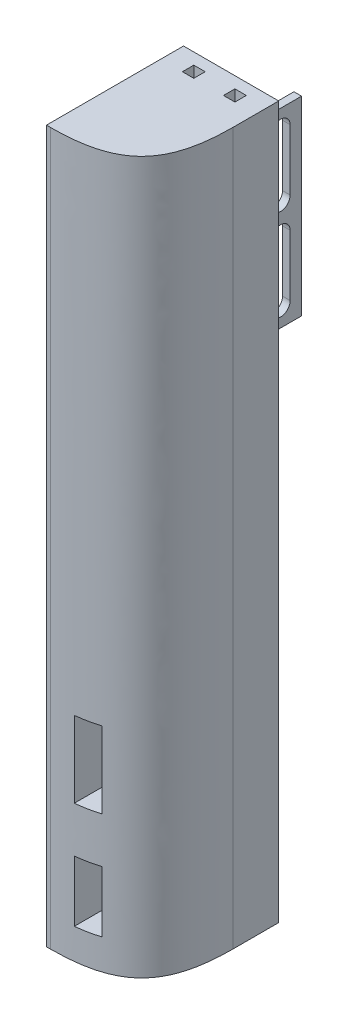
SolidWorks part; units mm, degrees
ref_plane "Front Plane" through (0, 0, 0) normal (0, 0, 1) x (1, 0, 0)
ref_plane "Top Plane" through (0, 0, 0) normal (0, 1, 0) x (1, 0, 0)
ref_plane "Right Plane" through (0, 0, 0) normal (1, 0, 0) x (0, 0, -1)
sketch "Sketch1" plane through (0, 0, 0) normal (0, 1, 0) x (1, 0, 0)
  line L1 (0, 0) -> (25, 0)
  line L2 (0, 0) -> (0, 36)
  line L3 (0, 36) -> (25, 36)
  line L4 (25, 0) -> (25, 36)
  dimension "D1" = 36
  dimension "D2" = 25
extrude "Boss-Extrude1" add sketch "Sketch1" along normal blind 186.9
fillet "Fillet1" radius 24 1 edges at (25, 93.45, 0) conic rho 0.55
sketch "Sketch2" plane through (0, 0, 0) normal (-1, 0, 0) x (0, 0, 1)
  line L0 (-24, 0) -> (0, 0) construction
  line L1 (-6.2, 83.2) -> (-1.2, 83.2)
  line L2 (-6.2, 83.2) -> (-6.2, 73.2)
  line L3 (-6.2, 73.2) -> (-1.2, 73.2)
  line L4 (-1.2, 83.2) -> (-1.2, 73.2)
  line L5 (0, 186.9) -> (0, 0) construction
  dimension "D1" = 73.2
  dimension "D2" = 1.2
  dimension "D3" = 5
  dimension "D4" = 10
extrude "Cut-Extrude1" cut sketch "Sketch2" against normal blind 4
sketch "Sketch3" plane through (0, 0, 0) normal (-1, 0, 0) x (0, 0, 1)
  line L1 (-14, 33.2) -> (-6, 33.2)
  line L2 (-14, 33.2) -> (-14, 28)
  line L3 (-14, 28) -> (-6, 28)
  line L4 (-6, 33.2) -> (-6, 28)
  line L5 (-36, 0) -> (0, 0) construction
  line L6 (0, 186.9) -> (0, 0) construction
  line L8 (-22, 33.2) -> (-30, 33.2)
  line L9 (-22, 33.2) -> (-22, 28)
  line L10 (-22, 28) -> (-30, 28)
  line L11 (-30, 33.2) -> (-30, 28)
  line L12 (-6, 61.2) -> (-14, 61.2)
  line L13 (-6, 61.2) -> (-6, 66.8)
  line L14 (-6, 66.8) -> (-14, 66.8)
  line L15 (-14, 61.2) -> (-14, 66.8)
  line L16 (-22, 66.8) -> (-30, 66.8)
  line L17 (-22, 66.8) -> (-22, 61.2)
  line L18 (-22, 61.2) -> (-30, 61.2)
  line L19 (-30, 66.8) -> (-30, 61.2)
  dimension "D1" = 28
  dimension "D2" = 6
  dimension "D3" = 8
  dimension "D4" = 5.2
  dimension "D5" = 8
  dimension "D6" = 8
  dimension "D7" = 28
  dimension "D8" = 5.6
  dimension "D9" = 8
  dimension "D10" = 6
  dimension "D11" = 8
  dimension "D12" = 5.6
  dimension "D13" = 8
extrude "Cut-Extrude2" cut sketch "Sketch3" against normal blind 10
sketch "Sketch4" plane through (0, 0, 0) normal (-1, 0, 0) x (0, 0, 1)
  line L0 (-36, 0) -> (0, 0) construction
  line L1 (-26, 160) -> (-67, 160)
  line L2 (-26, 160) -> (-26, 110)
  line L3 (-26, 110) -> (-67, 110)
  line L4 (-67, 160) -> (-67, 110)
  line L5 (-36, 186.9) -> (-36, 0) construction
  dimension "D1" = 160
  dimension "D2" = 10
  dimension "D3" = 31
  dimension "D4" = 110
extrude "Boss-Extrude2" add sketch "Sketch4" along normal blind 2
sketch "Sketch5" plane through (-2, 0, 0) normal (-1, 0, 0) x (0, 0, 1)
  line L0 (-67, 110) -> (-26, 110) construction
  line L1 (-67, 160) -> (-67, 110) construction
  line L4 (-59, 131) -> (-59, 115)
  line L6 (-64, 131) -> (-64, 115)
  line L7 (-26, 160) -> (-67, 160) construction
  line L9 (-64, 139) -> (-64, 155)
  line L11 (-59, 139) -> (-59, 155)
  arc A0 (-64, 115) -> (-59, 115) centre (-61.5, 115) ccw
  arc A2 (-59, 131) -> (-64, 131) centre (-61.5, 131) ccw
  arc A3 (-59, 155) -> (-64, 155) centre (-61.5, 155) ccw
  arc A4 (-64, 139) -> (-59, 139) centre (-61.5, 139) ccw
  dimension "D1" = 5
  dimension "D4" = 16
  dimension "D5" = 16
  dimension "D2" = 5
  dimension "D3" = 5.5
  dimension "D6" = 5
extrude "Cut-Extrude3" cut sketch "Sketch5" against normal up to next
chamfer "Chamfer1" distance 16 angle 45 1 edges at (0, 135, -36)
sketch "Sketch6" plane through (0, 0, -36) normal (0, 0, -1) x (-1, 0, 0)
  line L0 (-25, 186.9) -> (-25, 0) construction
  line L1 (-21, 182.9) -> (-15, 182.9)
  line L2 (-21, 182.9) -> (-21, 178.9)
  line L3 (-21, 178.9) -> (-15, 178.9)
  line L4 (-15, 182.9) -> (-15, 178.9)
  line L5 (-25, 186.9) -> (0, 186.9) construction
  line L6 (-1, 186.9) -> (-25, 186.9) construction
  line L7 (-10.2, 182.9) -> (-4.2, 182.9)
  line L8 (-10.2, 182.9) -> (-10.2, 178.9)
  line L9 (-10.2, 178.9) -> (-4.2, 178.9)
  line L10 (-4.2, 182.9) -> (-4.2, 178.9)
  dimension "D1" = 4
  dimension "D2" = 4
  dimension "D3" = 4
  dimension "D4" = 6
  dimension "D5" = 6
  dimension "D6" = 4.8
  dimension "D7" = 4
extrude "Cut-Extrude4" cut sketch "Sketch6" against normal blind 9
sketch "Sketch7" plane through (0, 186.9, 0) normal (0, 1, 0) x (1, 0, 0)
  line L0 (25, 24) -> (25, 36) construction
  line L1 (19.5, 33) -> (16.5, 33)
  line L2 (19.5, 33) -> (19.5, 30)
  line L3 (19.5, 30) -> (16.5, 30)
  line L4 (16.5, 33) -> (16.5, 30)
  line L5 (25, 36) -> (0, 36) construction
  line L7 (8.7, 33) -> (5.7, 33)
  line L8 (8.7, 33) -> (8.7, 30)
  line L9 (8.7, 30) -> (5.7, 30)
  line L10 (5.7, 33) -> (5.7, 30)
  dimension "D1" = 5.5
  dimension "D2" = 3
  dimension "D3" = 3
  dimension "D4" = 3
  dimension "D5" = 3
  dimension "D6" = 3
  dimension "D7" = 3
  dimension "D8" = 7.8
extrude "Cut-Extrude5" cut sketch "Sketch7" against normal blind 10
sketch "Sketch8" plane through (0, 0, 0) normal (0, -1, 0) x (1, 0, 0)
  line L0 (25, -36) -> (0, -36) construction
  line L1 (3, -5) -> (7, -5)
  line L2 (3, -5) -> (3, -33)
  line L3 (3, -33) -> (7, -33)
  line L4 (7, -5) -> (7, -29)
  line L5 (0, -36) -> (0, 0) construction
  line L6 (25, -24) -> (25, -36) construction
  line L7 (7, -33) -> (21, -33)
  line L9 (7, -29) -> (21, -29)
  line L10 (21, -33) -> (21, -29)
  dimension "D1" = 5
  dimension "D2" = 3
  dimension "D3" = 3
  dimension "D4" = 4
  dimension "D5" = 4
  dimension "D6" = 4
  dimension "D7" = 14
  dimension "D8" = 28
extrude "Boss-Extrude3" add sketch "Sketch8" along normal blind 4
sketch "Sketch9" plane through (0, 0, 0) normal (0, -1, 0) x (1, 0, 0)
  line L0 (21, -29) -> (7, -29) construction
  line L1 (7, -29) -> (7, -5) construction
  circle A0 centre (14, -22) radius 2
  dimension "D1" = 4
  dimension "D2" = 7
  dimension "D3" = 7
extrude "Cut-Extrude6" cut sketch "Sketch9" against normal blind 5
sketch "Sketch10" plane through (0, 0, 0) normal (0, -1, 0) x (1, 0, 0)
  line L0 (7, -29) -> (7, -5) construction
  circle A0 centre (14, -12) radius 1.5
  circle A1 centre (14, -22) radius 2 construction
  dimension "D1" = 7
  dimension "D2" = 10
  dimension "D3" = 3
extrude "Cut-Extrude7" cut sketch "Sketch10" against normal blind 4
sketch "Sketch11" plane through (0, 0, 0) normal (0, 0, 1) x (1, 0, 0)
  line L0 (0, 186.9) -> (0, 0) construction
  line L1 (7, 24) -> (13, 24)
  line L2 (7, 24) -> (7, 8)
  line L3 (7, 8) -> (13, 8)
  line L4 (13, 24) -> (13, 8)
  line L5 (0, 0) -> (1, 0) construction
  line L7 (7, 36) -> (13, 36)
  line L8 (7, 36) -> (7, 56)
  line L9 (7, 56) -> (13, 56)
  line L10 (13, 36) -> (13, 56)
  dimension "D1" = 7
  dimension "D2" = 8
  dimension "D3" = 16
  dimension "D4" = 6
  dimension "D5" = 12
  dimension "D6" = 6
  dimension "D7" = 20
  dimension "D8" = 7
extrude "Cut-Extrude8" cut sketch "Sketch11" against normal blind 8
